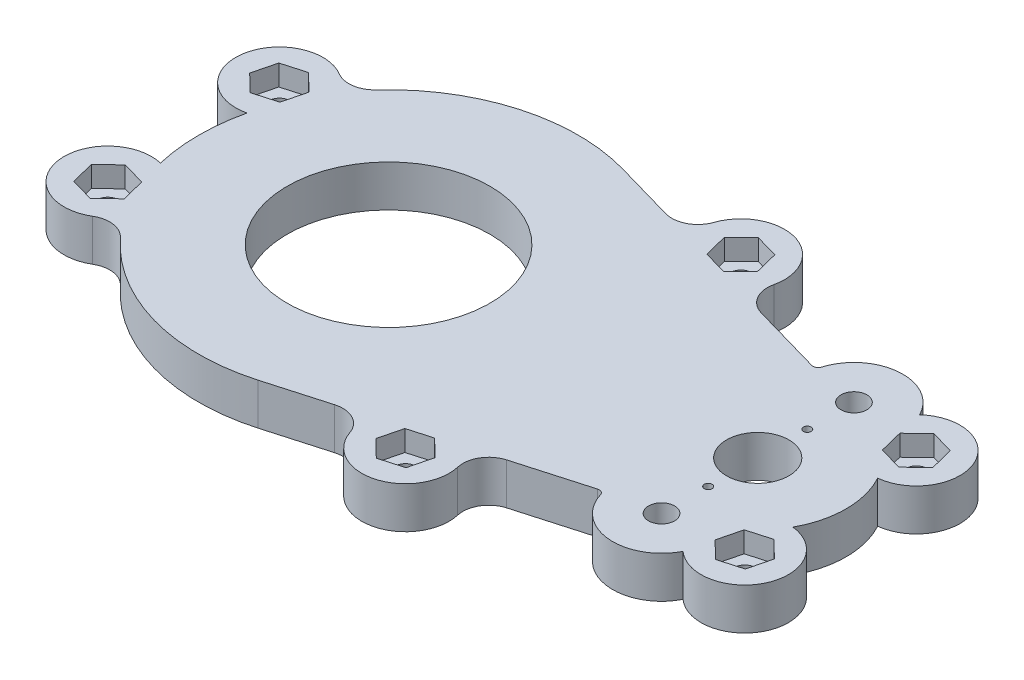
SolidWorks part; units mm, degrees
ref_plane "Front Plane" through (0, 0, 0) normal (0, 0, 1) x (1, 0, 0)
ref_plane "Top Plane" through (0, 0, 0) normal (0, 1, 0) x (1, 0, 0)
ref_plane "Right Plane" through (0, 0, 0) normal (1, 0, 0) x (0, 0, -1)
sketch "Sketch1" plane through (0, 0, 0) normal (0, 1, 0) x (1, 0, 0)
  line L0 (0, 73.0538) -> (0, -65.1274) construction
  line L1 (35.5, 6.365) -> (-28.5632, 24.502) construction
  line L2 (-70.6215, 0) -> (67.3742, 0) construction
  line L3 (35.5, -6.365) -> (-28.5632, -24.502) construction
  line L4 (4.5177, -15.1364) -> (0.1592, 0.2585)
  line L5 (0.1592, 0.2585) -> (4.6815, 1.5388)
  line L6 (4.6815, 1.5388) -> (9.04, -13.8561)
  line L7 (9.04, -13.8561) -> (9.5848, -15.7805)
  line L8 (9.5848, -15.7805) -> (5.0625, -17.0608)
  line L9 (5.0625, -17.0608) -> (4.5177, -15.1364)
  line L10 (-35.5, 0) -> (-60.5, 0) construction
  line L11 (-35.5, 0) -> (-35.5, 25) construction
  line L13 (-100, -75) -> (100, -75)
  line L14 (-100, -75) -> (-100, 75)
  line L15 (-100, 75) -> (100, 75)
  line L16 (100, -75) -> (100, 75)
  line L17 (-100, -75) -> (100, 75) construction
  line L18 (-100, 75) -> (100, -75) construction
  circle A0 centre (35.5, 0) radius 6
  circle A1 centre (-35.5, 0) radius 13.5
  circle A2 centre (-35.5, 0) radius 25.465 construction
  circle A3 centre (35.5, 0) radius 6.365 construction
  circle A4 centre (-60.5, 0) radius 2
  circle A5 centre (-35.5, 25) radius 2
  circle A6 centre (-10.5, 0) radius 2
  circle A7 centre (-35.5, -25) radius 2
  circle A8 centre (35.5, 18.5) radius 2.5
  circle A9 centre (35.5, -18.5) radius 2.5
  point P35 (0, 0)
  dimension "D1" = 12
  dimension "D2" = 27
  dimension "D5" = 50.93
  dimension "D6" = 12.73
  dimension "D12" = 4
  dimension "D19" = 5
  dimension "D3" = 71
  dimension "D4" = 35.5
  dimension "D7" = 90
  dimension "D8" = 27.5
  dimension "D9" = 4.7
  dimension "D10" = 16
  dimension "D11" = 2
  dimension "D13" = 25
  dimension "D15" = 90
  dimension "D16" = 25
  dimension "D17" = 200
  dimension "D18" = 150
  dimension "D20" = 18.5
  dimension "D14" = 4
extrude "Boss-Extrude1" add sketch "Sketch1" along normal blind 4
sketch "Sketch3" plane through (0, 4, 0) normal (0, 1, 0) x (1, 0, 0)
  line L0 (-26.5739, 31.2502) -> (39.0704, 12.5001)
  line L1 (-100, -75) -> (100, -75)
  line L2 (-100, -75) -> (-100, 75)
  line L3 (-100, 75) -> (100, 75)
  line L4 (100, -75) -> (100, 75)
  line L5 (-35.5, 0) -> (35.5, 0) construction
  line L6 (-26.5739, -31.2502) -> (39.0704, -12.5001)
  arc A0 (-26.5739, 31.2502) -> (-26.5739, -31.2502) centre (-35.5, 0) ccw
  arc A1 (39.0704, -12.5001) -> (39.0704, 12.5001) centre (35.5, 0) ccw
  dimension "D1" = 65
  dimension "D2" = 26
extrude "Boss-Extrude2" add sketch "Sketch3" along normal blind 8.25
sketch "Sketch6" plane through (0, 12.25, 0) normal (0, 1, 0) x (1, 0, 0)
  circle A0 centre (35.5, 18.5) radius 5.4
  circle A1 centre (35.5, -18.5) radius 5.4
  dimension "D1" = 10.8
extrude "Cut-Extrude2" cut sketch "Sketch6" against normal up to surface (8.25 mm away) up to face at (-35.5, 4, 27)
fillet "Fillet1" radius 2.5 4 edges at (9.5848, 2, 15.7805) (5.0625, 2, 17.0608) (4.6815, 2, -1.5388) (0.1592, 2, -0.2585)
fillet "Fillet2" radius 5 4 edges at (36.5847, 8.125, 13.2101) (31.7849, 8.125, 14.5811) (36.5847, 8.125, -13.2101) (31.7849, 8.125, -14.5811)
sketch "Sketch2" plane through (0, 4, 0) normal (0, 1, 0) x (1, 0, 0)
  line L0 (29.5, 0) -> (41.5, 0) construction
  line L1 (35.5, 0) -> (35.5, -6) construction
  line L2 (35.5, 0) -> (35.5, 6) construction
  circle A0 centre (-35.5, 25) radius 4.4
  circle A1 centre (-10.5, 0) radius 4.4
  circle A2 centre (-35.5, -25) radius 4.4
  circle A3 centre (-60.5, 0) radius 4.4
  circle A4 centre (35.5, 0) radius 6 construction
  circle A7 centre (35.5, 18.5) radius 5.4
  circle A8 centre (35.5, -18.5) radius 5.4
  arc A9 (40.6003, 16.7261) -> (30.3389, 20.0883) centre (35.5, 18.5) ccw construction
  dimension "D1" = 8.8
extrude "Cut-Extrude1" cut sketch "Sketch2" against normal blind 2
sketch "Sketch8" plane through (0, 0, 0) normal (0, -1, 0) x (1, 0, 0)
  line L0 (-35.5, 0) -> (-100, 0) construction
  line L1 (-100, -75) -> (-100, 75) construction
  line L2 (-35.5, 0) -> (100, 0) construction
  line L3 (100, 75) -> (100, -75) construction
  line L4 (49.5, 21.4955) -> (49.5, -20.5045) construction
  line L5 (0, 32.8542) -> (0, -34.16) construction
  line L6 (-73, 27.0496) -> (-73, -26.9504) construction
  line L11 (-26.5739, -31.2502) -> (24.1868, -16.7513)
  line L12 (24.1868, 16.7513) -> (-26.5739, 31.2502)
  line L13 (-26.5739, -31.2502) -> (24.1868, -16.7513) construction
  line L14 (24.1868, 16.7513) -> (-26.5739, 31.2502) construction
  circle A0 centre (-35.5, 0) radius 32.5 construction
  arc A1 (-26.5739, 31.2502) -> (-26.5739, -31.2502) centre (-35.5, 0) ccw construction
  circle A13 centre (49.5, 16.5) radius 2
  circle A14 centre (-73, 16.5) radius 2
  circle A15 centre (0, 32.25) radius 2
  circle A16 centre (49.5, 16.5) radius 4.4 construction
  circle A17 centre (0, 32.25) radius 4.4 construction
  circle A18 centre (-73, 16.5) radius 4.4 construction
  circle A19 centre (35.5, 18.5) radius 5.4 construction
  arc A20 (40.6003, 16.7261) -> (30.3389, 20.0883) centre (35.5, 18.5) ccw construction
  circle A21 centre (35.5, -18.5) radius 5.4 construction
  circle A22 centre (-73, -16.5) radius 4.4 construction
  circle A23 centre (-73, -16.5) radius 2
  circle A24 centre (0, -32.25) radius 4.4 construction
  circle A25 centre (0, -32.25) radius 2
  circle A26 centre (49.5, -16.5) radius 4.4 construction
  circle A27 centre (49.5, -16.5) radius 2
  circle A28 centre (49.5, 16.5) radius 8.4 construction
  circle A29 centre (0, 32.25) radius 8.4 construction
  circle A30 centre (-73, 16.5) radius 8.4 construction
  arc A44 (30.3389, -20.0883) -> (40.6003, -16.7261) centre (35.5, -18.5) ccw
  arc A45 (42.5943, -10.8936) -> (40.6003, -16.7261) centre (45.3228, -15.0835) ccw
  arc A46 (42.5943, -10.8936) -> (42.5943, 10.8936) centre (35.5, 0) ccw
  arc A47 (40.6003, 16.7261) -> (42.5943, 10.8936) centre (45.3228, 15.0835) ccw
  arc A48 (30.3389, -20.0883) -> (24.1868, -16.7513) centre (25.5601, -21.559) ccw
  arc A49 (40.6003, 16.7261) -> (30.3389, 20.0883) centre (35.5, 18.5) ccw
  arc A50 (24.1868, 16.7513) -> (30.3389, 20.0883) centre (25.5601, 21.559) ccw
  arc A51 (-26.5739, 31.2502) -> (-26.5739, -31.2502) centre (-35.5, 0) ccw
  arc A52 (30.3389, -20.0883) -> (40.6003, -16.7261) centre (35.5, -18.5) ccw construction
  arc A53 (42.5943, -10.8936) -> (40.6003, -16.7261) centre (45.3228, -15.0835) ccw construction
  arc A54 (42.5943, -10.8936) -> (42.5943, 10.8936) centre (35.5, 0) ccw construction
  arc A55 (40.6003, 16.7261) -> (42.5943, 10.8936) centre (45.3228, 15.0835) ccw construction
  arc A56 (30.3389, -20.0883) -> (24.1868, -16.7513) centre (25.5601, -21.559) ccw construction
  arc A57 (40.6003, 16.7261) -> (30.3389, 20.0883) centre (35.5, 18.5) ccw construction
  arc A58 (24.1868, 16.7513) -> (30.3389, 20.0883) centre (25.5601, 21.559) ccw construction
  arc A59 (-26.5739, 31.2502) -> (-26.5739, -31.2502) centre (-35.5, 0) ccw construction
  dimension "D1" = 0
  dimension "D2" = 4
  dimension "D4" = 33
  dimension "D5" = 49.5
  dimension "D3" = 8.8
  dimension "D8" = 16.8
  dimension "D6" = 64.5
  dimension "D7" = 73
extrude "Cut-Extrude3" cut sketch "Sketch8" against normal through all both and the other way through all
sketch "Sketch13" plane through (0, 12.25, 0) normal (0, 1, 0) x (1, 0, 0)
  line L0 (-100, 0) -> (100, 0) construction
  line L1 (-100, 75) -> (-100, -75) construction
  line L2 (100, -75) -> (100, 75) construction
  line L5 (-8.1313, 30.1424) -> (-25.4754, 35.0964)
  line L6 (5.7914, -26.1656) -> (25.2854, -20.5975)
  line L7 (-25.4754, -35.0964) -> (25.2854, -20.5975)
  line L8 (25.2854, 20.5975) -> (-25.4754, 35.0964)
  line L9 (-25.4754, -35.0964) -> (-8.1313, -30.1424)
  line L10 (25.2854, 20.5975) -> (5.7914, 26.1656)
  arc A0 (5.7914, 26.1656) -> (-8.1313, 30.1424) centre (0, 32.25) ccw
  arc A1 (50.4188, 8.1504) -> (43.8854, 22.7479) centre (49.5, 16.5) ccw
  arc A2 (-65.6518, 20.5699) -> (-71.0361, 8.3328) centre (-73, 16.5) ccw
  arc A3 (-65.6518, -20.5699) -> (-71.0361, -8.3328) centre (-73, -16.5) cw
  arc A4 (5.7914, -26.1656) -> (-8.1313, -30.1424) centre (0, -32.25) cw
  arc A5 (50.4188, -8.1504) -> (43.8854, -22.7479) centre (49.5, -16.5) cw
  arc A14 (-71.0361, 8.3328) -> (-71.0361, -8.3328) centre (-35.5, 0) ccw
  arc A15 (-65.6518, -20.5699) -> (-25.4754, -35.0964) centre (-35.5, 0) ccw
  arc A22 (44.3783, 15.412) -> (26.5158, 21.2649) centre (35.5, 18.5) ccw
  arc A23 (44.3783, 15.412) -> (44.7771, 14.2455) centre (45.3228, 15.0835) ccw
  arc A24 (44.7771, -14.2455) -> (44.7771, 14.2455) centre (35.5, 0) ccw
  arc A25 (44.7771, -14.2455) -> (44.3783, -15.412) centre (45.3228, -15.0835) ccw
  arc A26 (26.5158, -21.2649) -> (44.3783, -15.412) centre (35.5, -18.5) ccw
  arc A27 (26.5158, -21.2649) -> (25.2854, -20.5975) centre (25.5601, -21.559) ccw
  arc A28 (-25.4754, 35.0964) -> (-25.4754, -35.0964) centre (-35.5, 0) ccw
  arc A29 (25.2854, 20.5975) -> (26.5158, 21.2649) centre (25.5601, 21.559) ccw
  arc A30 (43.8854, 22.7479) -> (26.5158, 21.2649) centre (35.5, 18.5) ccw
  arc A32 (50.4188, -8.1504) -> (50.4188, 8.1504) centre (35.5, 0) ccw
  arc A34 (26.5158, -21.2649) -> (43.8854, -22.7479) centre (35.5, -18.5) ccw
  arc A35 (26.5158, -21.2649) -> (25.2854, -20.5975) centre (25.5601, -21.559) ccw
  arc A36 (-25.4754, 35.0964) -> (-65.6518, 20.5699) centre (-35.5, 0) ccw
  arc A37 (25.2854, 20.5975) -> (26.5158, 21.2649) centre (25.5601, 21.559) ccw
  dimension "D1" = 16.8
  dimension "D2" = 4
extrude "Cut-Extrude6" cut sketch "Sketch13" against normal through all both and the other way through all flip side to cut
fillet "Fillet4" radius 5 6 edges at (-65.6518, 6.125, 20.5699) (-65.6518, 6.125, -20.5699) (-8.1313, 6.125, -30.1424) (5.7914, 6.125, -26.1656) (5.7914, 6.125, 26.1656) (-8.1313, 6.125, 30.1424)
sketch "Sketch16" plane through (0, 12.25, 0) normal (0, 1, 0) x (1, 0, 0)
  line L12 (-25.4754, -35.0964) -> (-14.035, -31.8287)
  line L13 (11.6951, -24.4793) -> (25.2854, -20.5975)
  line L14 (25.2854, 20.5975) -> (11.6951, 24.4793)
  line L15 (-14.035, 31.8287) -> (-25.4754, 35.0964)
  line L16 (-25.4754, -35.0964) -> (-14.035, -31.8287)
  line L17 (11.6951, -24.4793) -> (25.2854, -20.5975)
  line L18 (25.2854, 20.5975) -> (11.6951, 24.4793)
  line L19 (-14.035, 31.8287) -> (-25.4754, 35.0964)
  arc A60 (-71.0361, 8.3328) -> (-71.0361, -8.3328) centre (-35.5, 0) ccw
  arc A61 (-71.0361, -8.3328) -> (-68.692, -23.7112) centre (-73, -16.5) ccw
  arc A62 (-62.4376, -24.6296) -> (-68.692, -23.7112) centre (-66.1277, -28.0035) ccw
  arc A63 (-62.4376, -24.6296) -> (-25.4754, -35.0964) centre (-35.5, 0) ccw
  arc A64 (-7.9372, -34.9997) -> (-14.035, -31.8287) centre (-12.6617, -36.6364) ccw
  arc A65 (-7.9372, -34.9997) -> (8.1921, -30.3926) centre (0, -32.25) ccw
  arc A66 (11.6951, -24.4793) -> (8.1921, -30.3926) centre (13.0683, -29.2871) ccw
  arc A67 (26.5158, -21.2649) -> (25.2854, -20.5975) centre (25.5601, -21.559) ccw
  arc A68 (26.5158, -21.2649) -> (43.8854, -22.7479) centre (35.5, -18.5) ccw
  arc A69 (43.8854, -22.7479) -> (50.4188, -8.1504) centre (49.5, -16.5) ccw
  arc A70 (50.4188, -8.1504) -> (50.4188, 8.1504) centre (35.5, 0) ccw
  arc A71 (50.4188, 8.1504) -> (43.8854, 22.7479) centre (49.5, 16.5) ccw
  arc A72 (43.8854, 22.7479) -> (26.5158, 21.2649) centre (35.5, 18.5) ccw
  arc A73 (25.2854, 20.5975) -> (26.5158, 21.2649) centre (25.5601, 21.559) ccw
  arc A74 (8.1921, 30.3926) -> (11.6951, 24.4793) centre (13.0683, 29.2871) ccw
  arc A75 (8.1921, 30.3926) -> (-7.9372, 34.9997) centre (0, 32.25) ccw
  arc A76 (-14.035, 31.8287) -> (-7.9372, 34.9997) centre (-12.6617, 36.6364) ccw
  arc A77 (-25.4754, 35.0964) -> (-62.4376, 24.6296) centre (-35.5, 0) ccw
  arc A78 (-68.692, 23.7112) -> (-62.4376, 24.6296) centre (-66.1277, 28.0035) ccw
  arc A79 (-68.692, 23.7112) -> (-71.0361, 8.3328) centre (-73, 16.5) ccw
  arc A80 (-71.0361, 8.3328) -> (-71.0361, -8.3328) centre (-35.5, 0) ccw
  arc A81 (-71.0361, -8.3328) -> (-68.692, -23.7112) centre (-73, -16.5) ccw
  arc A82 (-62.4376, -24.6296) -> (-68.692, -23.7112) centre (-66.1277, -28.0035) ccw
  arc A83 (-62.4376, -24.6296) -> (-25.4754, -35.0964) centre (-35.5, 0) ccw
  arc A84 (-7.9372, -34.9997) -> (-14.035, -31.8287) centre (-12.6617, -36.6364) ccw
  arc A85 (-7.9372, -34.9997) -> (8.1921, -30.3926) centre (0, -32.25) ccw
  arc A86 (11.6951, -24.4793) -> (8.1921, -30.3926) centre (13.0683, -29.2871) ccw
  arc A87 (26.5158, -21.2649) -> (25.2854, -20.5975) centre (25.5601, -21.559) ccw
  arc A88 (26.5158, -21.2649) -> (43.8854, -22.7479) centre (35.5, -18.5) ccw
  arc A89 (43.8854, -22.7479) -> (50.4188, -8.1504) centre (49.5, -16.5) ccw
  arc A90 (50.4188, -8.1504) -> (50.4188, 8.1504) centre (35.5, 0) ccw
  arc A91 (50.4188, 8.1504) -> (43.8854, 22.7479) centre (49.5, 16.5) ccw
  arc A92 (43.8854, 22.7479) -> (26.5158, 21.2649) centre (35.5, 18.5) ccw
  arc A93 (25.2854, 20.5975) -> (26.5158, 21.2649) centre (25.5601, 21.559) ccw
  arc A94 (8.1921, 30.3926) -> (11.6951, 24.4793) centre (13.0683, 29.2871) ccw
  arc A95 (8.1921, 30.3926) -> (-7.9372, 34.9997) centre (0, 32.25) ccw
  arc A96 (-14.035, 31.8287) -> (-7.9372, 34.9997) centre (-12.6617, 36.6364) ccw
  arc A97 (-25.4754, 35.0964) -> (-62.4376, 24.6296) centre (-35.5, 0) ccw
  arc A98 (-68.692, 23.7112) -> (-62.4376, 24.6296) centre (-66.1277, 28.0035) ccw
  arc A99 (-68.692, 23.7112) -> (-71.0361, 8.3328) centre (-73, 16.5) ccw
  dimension "D1" = 0
extrude "Cut-Extrude7" cut sketch "Sketch16" against normal up to surface (10.25 mm away) up to face at (-35.5, 2, -23)
sketch "Sketch17" plane through (0, 0, 0) normal (0, -1, 0) x (1, 0, 0)
  line L4 (4.3815, 14.6553) -> (0.8403, 2.1469)
  line L5 (5.3625, 0.8666) -> (8.9038, 13.375)
  line L6 (4.3815, 14.6553) -> (0.8403, 2.1469)
  line L7 (5.3625, 0.8666) -> (8.9038, 13.375)
  circle A6 centre (-10.5, 0) radius 2
  circle A7 centre (-10.5, 0) radius 2
  arc A8 (2.4216, -0.8943) -> (5.3625, 0.8666) centre (2.9571, 1.5477) ccw
  arc A9 (0.8403, 2.1469) -> (2.4216, -0.8943) centre (3.2457, 1.4659) ccw
  arc A10 (8.9038, 13.375) -> (7.3224, 16.4163) centre (6.4983, 14.056) ccw
  arc A11 (7.3224, 16.4163) -> (4.3815, 14.6553) centre (6.787, 13.9743) ccw
  arc A12 (2.4216, -0.8943) -> (5.3625, 0.8666) centre (2.9571, 1.5477) ccw
  arc A13 (0.8403, 2.1469) -> (2.4216, -0.8943) centre (3.2457, 1.4659) ccw
  arc A14 (8.9038, 13.375) -> (7.3224, 16.4163) centre (6.4983, 14.056) ccw
  arc A15 (7.3224, 16.4163) -> (4.3815, 14.6553) centre (6.787, 13.9743) ccw
  circle A17 centre (-35.5, -25) radius 2
  circle A18 centre (-35.5, -25) radius 2
  circle A20 centre (-35.5, 25) radius 2
  circle A21 centre (-35.5, 25) radius 2
  circle A23 centre (-60.5, 0) radius 2
  circle A24 centre (-60.5, 0) radius 2
  dimension "D1" = 0
  dimension "D2" = 0
  dimension "D3" = 0
  dimension "D4" = 0
  dimension "D5" = 0
extrude "Boss-Extrude3" add sketch "Sketch17" against normal up to surface (2 mm away) up to face at (35.5, 2, -16)
sketch "Sketch18" plane through (0, 2, 0) normal (0, 1, 0) x (1, 0, 0)
  line L8 (-25.4754, -35.0964) -> (-14.035, -31.8287)
  line L9 (11.6951, -24.4793) -> (25.2854, -20.5975)
  line L10 (25.2854, 20.5975) -> (11.6951, 24.4793)
  line L11 (-14.035, 31.8287) -> (-25.4754, 35.0964)
  line L12 (-25.4754, -35.0964) -> (-14.035, -31.8287)
  line L13 (11.6951, -24.4793) -> (25.2854, -20.5975)
  line L14 (25.2854, 20.5975) -> (11.6951, 24.4793)
  line L15 (-14.035, 31.8287) -> (-25.4754, 35.0964)
  circle A20 centre (-35.5, 0) radius 13.5
  circle A21 centre (0, 32.25) radius 2
  circle A22 centre (-73, 16.5) radius 2
  circle A23 centre (-73, -16.5) radius 2
  circle A24 centre (0, 32.25) radius 2 construction
  circle A25 centre (-35.5, 0) radius 13.5 construction
  circle A26 centre (0, -32.25) radius 2
  circle A27 centre (35.5, -18.5) radius 2.5
  circle A28 centre (35.5, 0) radius 6
  circle A29 centre (49.5, -16.5) radius 2
  circle A30 centre (35.5, 18.5) radius 2.5
  circle A31 centre (49.5, 16.5) radius 2
  circle A32 centre (-73, 16.5) radius 2 construction
  circle A33 centre (-73, -16.5) radius 2 construction
  circle A34 centre (0, -32.25) radius 2 construction
  circle A35 centre (35.5, -18.5) radius 2.5 construction
  circle A36 centre (35.5, 0) radius 6 construction
  circle A37 centre (35.5, 18.5) radius 2.5 construction
  circle A38 centre (49.5, 16.5) radius 2 construction
  circle A39 centre (49.5, -16.5) radius 2 construction
  arc A40 (-68.692, 23.7112) -> (-71.0361, 8.3328) centre (-73, 16.5) ccw
  arc A41 (-71.0361, 8.3328) -> (-71.0361, -8.3328) centre (-35.5, 0) ccw
  arc A42 (-71.0361, -8.3328) -> (-68.692, -23.7112) centre (-73, -16.5) ccw
  arc A43 (-62.4376, -24.6296) -> (-68.692, -23.7112) centre (-66.1277, -28.0035) ccw
  arc A44 (-62.4376, -24.6296) -> (-25.4754, -35.0964) centre (-35.5, 0) ccw
  arc A45 (-7.9372, -34.9997) -> (-14.035, -31.8287) centre (-12.6617, -36.6364) ccw
  arc A46 (-7.9372, -34.9997) -> (8.1921, -30.3926) centre (0, -32.25) ccw
  arc A47 (11.6951, -24.4793) -> (8.1921, -30.3926) centre (13.0683, -29.2871) ccw
  arc A48 (26.5158, -21.2649) -> (25.2854, -20.5975) centre (25.5601, -21.559) ccw
  arc A49 (26.5158, -21.2649) -> (43.8854, -22.7479) centre (35.5, -18.5) ccw
  arc A50 (43.8854, -22.7479) -> (50.4188, -8.1504) centre (49.5, -16.5) ccw
  arc A51 (50.4188, -8.1504) -> (50.4188, 8.1504) centre (35.5, 0) ccw
  arc A52 (50.4188, 8.1504) -> (43.8854, 22.7479) centre (49.5, 16.5) ccw
  arc A53 (43.8854, 22.7479) -> (26.5158, 21.2649) centre (35.5, 18.5) ccw
  arc A54 (25.2854, 20.5975) -> (26.5158, 21.2649) centre (25.5601, 21.559) ccw
  arc A55 (8.1921, 30.3926) -> (11.6951, 24.4793) centre (13.0683, 29.2871) ccw
  arc A56 (8.1921, 30.3926) -> (-7.9372, 34.9997) centre (0, 32.25) ccw
  arc A57 (-14.035, 31.8287) -> (-7.9372, 34.9997) centre (-12.6617, 36.6364) ccw
  arc A58 (-25.4754, 35.0964) -> (-62.4376, 24.6296) centre (-35.5, 0) ccw
  arc A59 (-68.692, 23.7112) -> (-62.4376, 24.6296) centre (-66.1277, 28.0035) ccw
  arc A60 (-68.692, 23.7112) -> (-71.0361, 8.3328) centre (-73, 16.5) ccw
  arc A61 (-71.0361, 8.3328) -> (-71.0361, -8.3328) centre (-35.5, 0) ccw
  arc A62 (-71.0361, -8.3328) -> (-68.692, -23.7112) centre (-73, -16.5) ccw
  arc A63 (-62.4376, -24.6296) -> (-68.692, -23.7112) centre (-66.1277, -28.0035) ccw
  arc A64 (-62.4376, -24.6296) -> (-25.4754, -35.0964) centre (-35.5, 0) ccw
  arc A65 (-7.9372, -34.9997) -> (-14.035, -31.8287) centre (-12.6617, -36.6364) ccw
  arc A66 (-7.9372, -34.9997) -> (8.1921, -30.3926) centre (0, -32.25) ccw
  arc A67 (11.6951, -24.4793) -> (8.1921, -30.3926) centre (13.0683, -29.2871) ccw
  arc A68 (26.5158, -21.2649) -> (25.2854, -20.5975) centre (25.5601, -21.559) ccw
  arc A69 (26.5158, -21.2649) -> (43.8854, -22.7479) centre (35.5, -18.5) ccw
  arc A70 (43.8854, -22.7479) -> (50.4188, -8.1504) centre (49.5, -16.5) ccw
  arc A71 (50.4188, -8.1504) -> (50.4188, 8.1504) centre (35.5, 0) ccw
  arc A72 (50.4188, 8.1504) -> (43.8854, 22.7479) centre (49.5, 16.5) ccw
  arc A73 (43.8854, 22.7479) -> (26.5158, 21.2649) centre (35.5, 18.5) ccw
  arc A74 (25.2854, 20.5975) -> (26.5158, 21.2649) centre (25.5601, 21.559) ccw
  arc A75 (8.1921, 30.3926) -> (11.6951, 24.4793) centre (13.0683, 29.2871) ccw
  arc A76 (8.1921, 30.3926) -> (-7.9372, 34.9997) centre (0, 32.25) ccw
  arc A77 (-14.035, 31.8287) -> (-7.9372, 34.9997) centre (-12.6617, 36.6364) ccw
  arc A78 (-25.4754, 35.0964) -> (-62.4376, 24.6296) centre (-35.5, 0) ccw
  arc A79 (-68.692, 23.7112) -> (-62.4376, 24.6296) centre (-66.1277, 28.0035) ccw
  dimension "D1" = 0
extrude "Boss-Extrude4" add sketch "Sketch18" along normal blind 6
sketch "Sketch19" plane through (0, 0, 0) normal (0, -1, 0) x (1, 0, 0)
  line L0 (25.975, 0) -> (45.025, 0) construction
  circle A0 centre (-35.5, 0) radius 19.5
  circle A1 centre (35.5, 0) radius 9.525 construction
  circle A2 centre (35.5, 9.525) radius 0.75
  circle A3 centre (35.5, -9.525) radius 0.75
  dimension "D1" = 39
  dimension "D2" = 19.05
  dimension "D3" = 1.5
extrude "Cut-Extrude8" cut sketch "Sketch19" against normal through all both and the other way through all
sketch "Sketch20" plane through (0, 0, 0) normal (0, -1, 0) x (1, 0, 0)
  line L1 (40.1188, 18.5) -> (37.8094, 22.5)
  line L2 (37.8094, 22.5) -> (33.1906, 22.5)
  line L3 (33.1906, 22.5) -> (30.8812, 18.5)
  line L4 (30.8812, 18.5) -> (33.1906, 14.5)
  line L5 (33.1906, 14.5) -> (37.8094, 14.5)
  line L6 (37.8094, 14.5) -> (40.1188, 18.5)
  line L7 (40.1188, -18.5) -> (37.8094, -14.5)
  line L8 (37.8094, -14.5) -> (33.1906, -14.5)
  line L9 (33.1906, -14.5) -> (30.8812, -18.5)
  line L10 (30.8812, -18.5) -> (33.1906, -22.5)
  line L11 (33.1906, -22.5) -> (37.8094, -22.5)
  line L12 (37.8094, -22.5) -> (40.1188, -18.5)
  circle A0 centre (35.5, 18.5) radius 4 construction
  circle A1 centre (35.5, -18.5) radius 4 construction
  dimension "D1" = 8
  dimension "D2" = 8
extrude "Cut-Extrude9" cut sketch "Sketch20" against normal blind 4
sketch "Sketch21" plane through (0, 8, 0) normal (0, 1, 0) x (1, 0, 0)
  line L0 (25.2854, 20.5975) -> (11.6951, 24.4793) construction
  line L1 (-69.6808, 13.2881) -> (-68.5588, 17.7685)
  line L2 (-68.5588, 17.7685) -> (-71.878, 20.9805)
  line L3 (-71.878, 20.9805) -> (-76.3192, 19.7119)
  line L4 (-76.3192, 19.7119) -> (-77.4412, 15.2315)
  line L5 (-77.4412, 15.2315) -> (-74.122, 12.0195)
  line L6 (-74.122, 12.0195) -> (-69.6808, 13.2881)
  line L7 (-69.6808, -13.2881) -> (-74.122, -12.0195)
  line L8 (-74.122, -12.0195) -> (-77.4412, -15.2315)
  line L9 (-77.4412, -15.2315) -> (-76.3192, -19.7119)
  line L10 (-76.3192, -19.7119) -> (-71.878, -20.9805)
  line L11 (-71.878, -20.9805) -> (-68.5588, -17.7685)
  line L12 (-68.5588, -17.7685) -> (-69.6808, -13.2881)
  line L13 (4.4412, 30.9815) -> (3.3192, 35.4619)
  line L14 (3.3192, 35.4619) -> (-1.122, 36.7305)
  line L15 (-1.122, 36.7305) -> (-4.4412, 33.5185)
  line L16 (-4.4412, 33.5185) -> (-3.3192, 29.0381)
  line L17 (-3.3192, 29.0381) -> (1.122, 27.7695)
  line L18 (1.122, 27.7695) -> (4.4412, 30.9815)
  line L19 (50.622, 12.0195) -> (53.9412, 15.2315)
  line L20 (53.9412, 15.2315) -> (52.8192, 19.7119)
  line L21 (52.8192, 19.7119) -> (48.378, 20.9805)
  line L22 (48.378, 20.9805) -> (45.0588, 17.7685)
  line L23 (45.0588, 17.7685) -> (46.1808, 13.2881)
  line L24 (46.1808, 13.2881) -> (50.622, 12.0195)
  line L25 (53.9412, -15.2315) -> (50.622, -12.0195)
  line L26 (50.622, -12.0195) -> (46.1808, -13.2881)
  line L27 (46.1808, -13.2881) -> (45.0588, -17.7685)
  line L28 (45.0588, -17.7685) -> (48.378, -20.9805)
  line L29 (48.378, -20.9805) -> (52.8192, -19.7119)
  line L30 (52.8192, -19.7119) -> (53.9412, -15.2315)
  line L31 (4.4412, -30.9815) -> (1.122, -27.7695)
  line L32 (1.122, -27.7695) -> (-3.3192, -29.0381)
  line L33 (-3.3192, -29.0381) -> (-4.4412, -33.5185)
  line L34 (-4.4412, -33.5185) -> (-1.122, -36.7305)
  line L35 (-1.122, -36.7305) -> (3.3192, -35.4619)
  line L36 (3.3192, -35.4619) -> (4.4412, -30.9815)
  line L37 (11.6951, -24.4793) -> (25.2854, -20.5975) construction
  line L38 (-25.4754, -35.0964) -> (-14.035, -31.8287) construction
  line L39 (-14.035, 31.8287) -> (-25.4754, 35.0964) construction
  circle A0 centre (-73, 16.5) radius 4 construction
  circle A1 centre (-73, -16.5) radius 4 construction
  circle A2 centre (0, 32.25) radius 4 construction
  circle A3 centre (49.5, 16.5) radius 4 construction
  circle A4 centre (49.5, -16.5) radius 4 construction
  circle A5 centre (0, -32.25) radius 4 construction
  point P46 (-70.2184, -19.3745)
  dimension "D1" = 8
  dimension "D2" = 8
  dimension "D3" = 8
  dimension "D4" = 8
  dimension "D5" = 8
  dimension "D6" = 8
extrude "Cut-Extrude10" cut sketch "Sketch21" against normal blind 4
